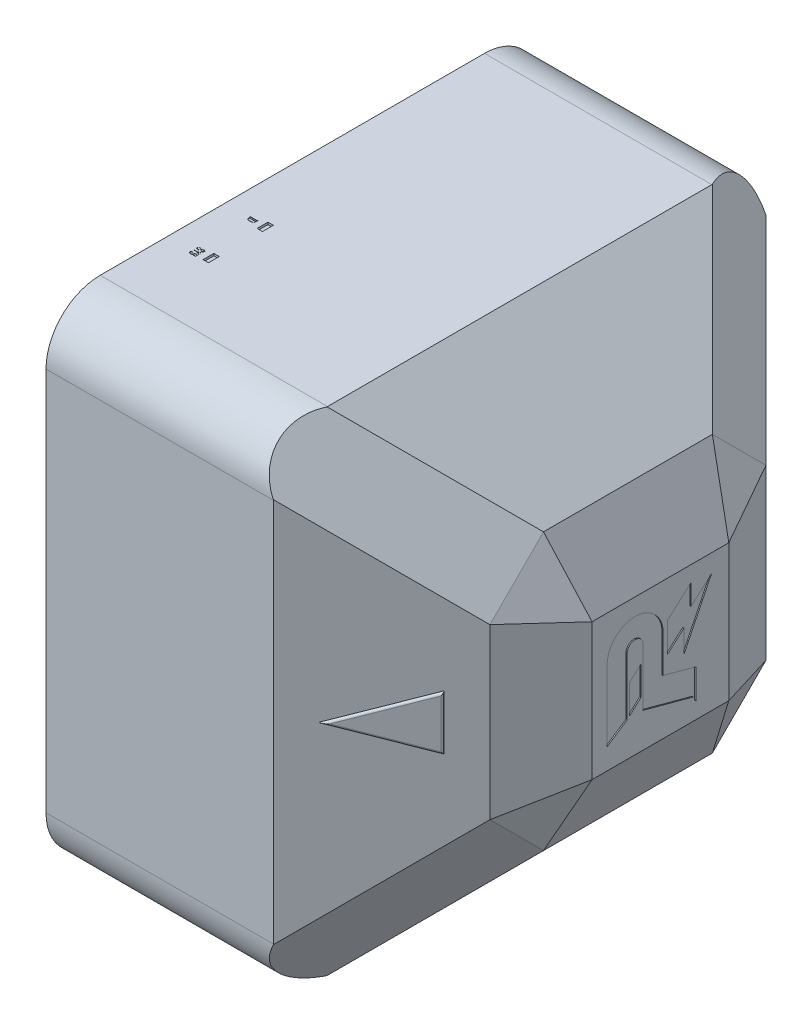
SolidWorks part; units mm, degrees
ref_plane "前视基准面" through (0, 0, 0) normal (0, 0, 1) x (1, 0, 0)
ref_plane "上视基准面" through (0, 0, 0) normal (0, 1, 0) x (1, 0, 0)
ref_plane "右视基准面" through (0, 0, 0) normal (1, 0, 0) x (0, 0, -1)
sketch "草图1" plane through (0, 0, 0) normal (1, 0, 0) x (0, 0, -1)
  line L1 (22.75, -22.75) -> (-22.75, -22.75)
  line L2 (22.75, -22.75) -> (22.75, 22.75)
  line L3 (22.75, 22.75) -> (-22.75, 22.75)
  line L4 (-22.75, -22.75) -> (-22.75, 22.75)
  line L5 (22.75, -22.75) -> (-22.75, 22.75) construction
  line L6 (22.75, 22.75) -> (-22.75, -22.75) construction
  point P0 (0, 0)
  dimension "D1" = 45.5
  dimension "D2" = 45.5
extrude "凸台-拉伸1" add sketch "草图1" along normal blind 31
chamfer "倒角1" distance 10 angle 45 4 edges at (31, 22.75, 0) (31, 0, -22.75) (31, -22.75, 0) (31, 0, 22.75)
fillet "圆角2" radius 5 4 edges at (10.5, 22.75, 22.75) (10.5, 22.75, -22.75) (10.5, -22.75, -22.75) (10.5, -22.75, 22.75)
sketch "草图4" plane through (31, 0, 0) normal (1, 0, 0) x (0, 0, -1)
  line L1 (12.75, -12.75) -> (-12.75, -12.75)
  line L2 (12.75, -12.75) -> (12.75, 12.75)
  line L3 (12.75, 12.75) -> (-12.75, 12.75)
  line L4 (-12.75, -12.75) -> (-12.75, 12.75)
  line L5 (12.75, -12.75) -> (-12.75, 12.75) construction
  line L6 (12.75, 12.75) -> (-12.75, -12.75) construction
  point P0 (0, 0)
extrude "凸台-拉伸2" add sketch "草图4" along normal blind 3
chamfer "倒角3" distance 3 angle 65 4 edges at (34, 12.75, 0) (34, 0, 12.75) (34, -12.75, 0) (34, 0, -12.75) first distance on face at (32.5, 12.75, 0) first distance on face at (32.5, 0, 12.75) first distance on face at (32.5, -12.75, 0) first distance on face at (32.5, 0, -12.75)
sketch "草图5" plane through (21.875, 0, 21.875) normal (0.7071, 0, 0.7071) x (0.7071, 0, -0.7071)
  line L0 (0, 0) -> (12.9047, 0) construction
  line L1 (12.9047, 12.75) -> (12.9047, -12.75) construction
  line L2 (1.7626, 0) -> (9.9047, 2.5)
  line L3 (9.9047, 2.5) -> (9.9047, -2.5)
  line L4 (9.9047, -2.5) -> (1.7626, 0)
  line L5 (-1.2374, -17.75) -> (-1.2374, 17.75) construction
  point P8 (9.9047, 0)
  dimension "D1" = 3
  dimension "D2" = 3
  dimension "D3" = 5
extrude "凸台-拉伸3" add sketch "草图5" along normal blind 0.2
fillet "圆角3" radius 0.2 3 edges at (26.1414, -1.25, 17.8914) (29.0201, 0, 15.0127) (26.1414, 1.25, 17.8914)
ref_plane "基准面1" through (31, 0, 0) normal (1, 0, 0) x (0, 0, -1)
sketch "草图6" plane through (31, 0, 0) normal (1, 0, 0) x (0, 0, -1)
  line L0 (12.75, -7.8003) -> (7.8003, -12.75)
  line L1 (12.75, -12.75) -> (12.75, 12.75) construction
  line L2 (-12.75, -12.75) -> (12.75, -12.75) construction
  line L3 (12.75, -7.8003) -> (12.75, -12.75)
  line L4 (12.75, -12.75) -> (7.8003, -12.75)
  dimension "D1" = 7
ref_plane "基准面2" through (21, 0, 0) normal (1, 0, 0) x (0, 0, -1)
sketch "草图7" plane through (21, 0, 0) normal (1, 0, 0) x (0, 0, -1)
  line L0 (17.8, -22.7497) -> (22.7497, -17.8)
  line L1 (22.7497, -17.8) -> (22.7497, -22.7497)
  line L2 (22.7497, -22.7497) -> (17.8, -22.7497)
  arc A0 (17.75, -22.75) -> (21.2855, -21.2855) centre (17.75, -17.75) ccw construction
  arc A1 (21.2855, -21.2855) -> (22.75, -17.75) centre (17.75, -17.75) ccw construction
  dimension "D1" = 7
ref_plane "基准面3" through (27.5165, -13.7586, -13.7586) normal (0.8165, -0.4083, -0.4083) x (-0.3652, 0.1826, -0.9129)
sketch "草图8" plane through (27.5165, -13.7586, -13.7586) normal (0.8165, -0.4083, -0.4083) x (-0.3652, 0.1826, -0.9129)
  line L1 (74.1456, -46.2304) -> (-83.4642, -46.2304)
  line L2 (74.1456, -46.2304) -> (74.1456, 61.6079)
  line L3 (74.1456, 61.6079) -> (-83.4642, 61.6079)
  line L4 (-83.4642, -46.2304) -> (-83.4642, 61.6079)
  line L5 (74.1456, -46.2304) -> (-83.4642, 61.6079) construction
  line L6 (74.1456, 61.6079) -> (-83.4642, -46.2304) construction
  point P0 (-4.6593, 7.6888)
extrude "切除-拉伸1" cut sketch "草图8" along normal blind 14.5
mirror "镜向1" about plane through (0, 0, 0) normal (0, 0, 1) of "切除-拉伸1"
mirror "镜向2" about plane through (0, 0, 0) normal (0, 1, 0) of "镜向1"
ref_axis "基准轴1" through (34, -6.3165, 6.3165) along (-0.4137, -0.2046, 0.8871)
ref_axis "基准轴2" through (31, -7.8003, 12.75) along (0, -0.7071, -0.7071)
ref_plane "基准面4" through (30.1337, -11.4182, 11.4182) normal (-0.8814, 0.334, -0.334) x (-0.3123, 0.1183, 0.9426)
sketch "草图10" plane through (30.1337, -11.4182, 11.4182) normal (-0.8814, 0.334, -0.334) x (-0.3123, 0.1183, 0.9426)
  line L1 (12.4751, -9.6377) -> (-15.4307, -9.6377)
  line L2 (12.4751, -9.6377) -> (12.4751, 13.4963)
  line L3 (12.4751, 13.4963) -> (-15.4307, 13.4963)
  line L4 (-15.4307, -9.6377) -> (-15.4307, 13.4963)
  line L5 (12.4751, -9.6377) -> (-15.4307, 13.4963) construction
  line L6 (12.4751, 13.4963) -> (-15.4307, -9.6377) construction
  point P0 (-1.4778, 1.9293)
extrude "切除-拉伸2" cut sketch "草图10" against normal blind 14.5
mirror "镜向3" about plane through (0, 0, 0) normal (0, 1, 0) of "切除-拉伸2"
mirror "镜向4" about plane through (0, 0, 0) normal (0, 0, 1) of "镜向3"
sketch "草图11" plane through (34, 0, 0) normal (1, 0, 0) x (0, 0, -1)
  line L0 (-4.9252, -4.3786) -> (-4.9252, 2.2791)
  line L1 (-4.9252, -4.3786) -> (-3.0665, -3.1474)
  line L2 (-3.0665, -3.1474) -> (-3.0665, 2.2791)
  line L6 (-1.5983, 2.2791) -> (-1.5983, -3.1257)
  line L7 (0.2489, 2.2791) -> (0.2489, -1.264)
  line L8 (0.2489, -1.264) -> (3.2675, -2.0841)
  line L9 (3.2675, -2.0841) -> (3.2675, -4.8404)
  line L10 (3.2675, -4.8404) -> (3.0491, -4.3786)
  line L11 (3.0491, -4.3786) -> (-1.5983, -3.1257)
  line L12 (-2.8665, -0.3016) -> (-1.7983, 0.6737)
  line L13 (-2.8665, -2.963) -> (-1.7983, -1.9783)
  line L14 (0.6489, 2.942) -> (2.8245, 4.8715)
  line L15 (2.8245, 4.8715) -> (2.8245, 2.9645)
  line L16 (2.8245, 2.9645) -> (4.7154, 4.6414)
  line L17 (4.7154, 4.6414) -> (2.1598, -0.5591)
  line L18 (2.1598, -0.5591) -> (2.1598, 1.5611)
  line L19 (2.1598, 1.5611) -> (0.6489, 0.2211)
  line L20 (-2.8665, -2.963) -> (-2.8665, -0.3016)
  line L21 (-1.7983, -1.9783) -> (-1.7983, 0.6737)
  line L22 (0.6489, 0.2211) -> (0.6489, 2.942)
  arc A0 (-4.9252, 2.2791) -> (0.2489, 2.2791) centre (-2.3382, 2.1541) cw
  arc A1 (-3.0665, 2.2791) -> (-1.5983, 2.2791) centre (-2.3324, 2.1483) cw
extrude "切除-拉伸3" cut sketch "草图11" against normal blind 0.1
hole_wizard "M3 螺纹孔1" positions "草图17" profile "草图19" tap size "M3" standard "GB"
sketch "草图17" plane through (0, 0, 0) normal (-1, 0, 0) x (0, 0, 1)
  line L0 (0, -19) -> (0, 0) construction
  line L1 (0, 0) -> (0, 19) construction
  point P0 (0, -19)
  point P2 (0, 19)
  dimension "D1" = 19
  dimension "D2" = 19
sketch "草图19" plane through (0, -19, 0) normal (0, 1, 0) x (0, 0, 1)
  line L0 (0, 0) -> (0, 6.2511)
  line L1 (0, 6.2511) -> (1.25, 5.5)
  line L2 (1.25, 5.5) -> (1.25, 0.275)
  line L3 (1.25, 0.275) -> (1.525, 0)
  line L5 (1.525, 0) -> (0, 0)
  line L6 (-1.25, 0.275) -> (-1.525, 0) construction
  line L10 (0, 6.2511) -> (-1.25, 5.5) construction
  line L11 (0, -6.35) -> (0, 107.95) construction
  dimension "螺纹孔钻头直径" = 2.5
  dimension "螺纹孔钻头深度" = 5.5
  dimension "近端锥形沉头孔直径" = 3.05
  dimension "近端锥形沉头孔角度" = 90
  dimension "导头角度" = 118
cosmetic thread "孔螺蚊线1" parameters "D1"=4, "D2"=3
cosmetic thread "孔螺蚊线2" parameters "D1"=4, "D2"=3
sketch "草图20" plane through (0, 0, -22.75) normal (0, 0, -1) x (-1, 0, 0)
  line L0 (0, -17.75) -> (0, 17.75) construction
  line L1 (0, -22.75) -> (-21, -22.75) construction
  circle A0 centre (-5, -7.75) radius 3.25
  dimension "D1" = 5
  dimension "D2" = 15
  dimension "D3" = 6.5
extrude "凸台-拉伸4" add sketch "草图20" along normal blind 9.1
sketch "草图21" plane through (0, 22.75, 0) normal (0, 1, 0) x (1, 0, 0)
  line L0 (0, 17.75) -> (0, -17.75) construction
  line L1 (3.5, -6.75) -> (4, -6.75)
  line L2 (3.5, -6.75) -> (3.5, -5.75)
  line L3 (3.5, -5.75) -> (4, -5.75)
  line L4 (4, -6.75) -> (4, -5.75)
  line L5 (21, -22.75) -> (0, -22.75) construction
  line L6 (3.5, -11.75) -> (3.5, -10.75)
  line L7 (4, -11.75) -> (4, -10.75)
  line L8 (3.5, -10.75) -> (4, -10.75)
  line L9 (3.5, -11.75) -> (4, -11.75)
  dimension "D1" = 3.5
  dimension "D2" = 17
  dimension "D3" = 0.5
  dimension "D4" = 1
  dimension "D6" = 6
  dimension "D5" = 2
extrude "切除-拉伸4" cut sketch "草图21" against normal blind 0.2
sketch "草图22" plane through (0, 22.75, 0) normal (0, 1, 0) x (1, 0, 0)
  line L0 (2.2169, -5.7116) -> (2.2169, -11.8042) construction
  text T0 " ID            SYS" font "汉仪长仿宋体" height 0.7
extrude "切除-拉伸5" cut sketch "草图22" against normal blind 0.2
